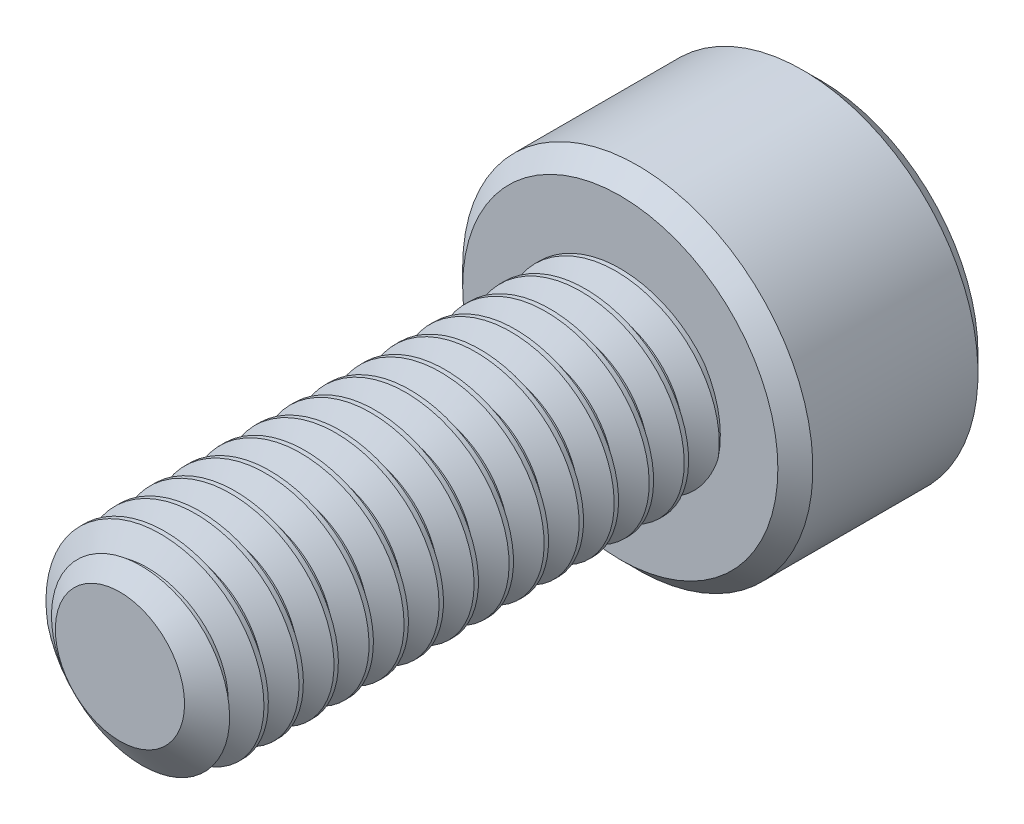
SolidWorks part; units mm, degrees
ref_plane "Front Plane" through (0, 0, 0) normal (0, 0, 1) x (1, 0, 0)
ref_plane "Top Plane" through (0, 0, 0) normal (0, 1, 0) x (1, 0, 0)
ref_plane "Right Plane" through (0, 0, 0) normal (1, 0, 0) x (0, 0, -1)
sketch "Sketch1" plane through (0, 0, 0) normal (0, 0, 1) x (1, 0, 0)
  circle A0 centre (0, 0) radius 2
  dimension "OD" = 4
extrude "Extrude1" add sketch "Sketch1" against normal blind 10
sketch "Sketch2" plane through (0, 0, 0) normal (0, 0, 1) x (1, 0, 0)
  circle A0 centre (0, 0) radius 2 construction
  circle A1 centre (0, 0) radius 2
curve "Helix/Spiral1" pitch 0.7 height 10.7 radius 2 centre (0, 0, 0) axis (0, 0, -1) start towards (0, 1, 0) parameters "pitch"=0.7
sketch "Sketch3" plane through (0, 0, 0) normal (1, 0, 0) x (0, 0, -1)
  line L0 (-0.6125, 2) -> (-0.35, 1.5453)
  line L1 (-0.35, 1.5453) -> (-0.2625, 1.5453)
  line L2 (-0.2625, 1.5453) -> (0, 2)
  line L3 (-0.6125, 2) -> (0, 2)
  line L4 (-0.3062, 2) -> (-0.3062, 1.5453) construction
  line L5 (-0.4812, 1.7727) -> (-0.1312, 1.7727) construction
  line L6 (0, 2) -> (0, -2) construction
  dimension "D1" = 0.0875
  dimension "D2" = 0.35
  dimension "D3" = 60
sweep "Cut-Sweep1" cut profiles "Sketch3" path "Helix/Spiral1" align with end faces yes
sketch "Sketch4" plane through (0, 0, 0) normal (1, 0, 0) x (0, 0, -1)
  line L0 (0.4962, 2) -> (0, 1.2913)
  line L1 (0, 1.2913) -> (0, 2)
  line L2 (0.4962, 2) -> (0, 2)
  line L3 (-0.6125, 2) -> (0, 2) construction
  line L4 (0, 0) -> (7.0209, 0) construction
  dimension "D1" = 55
  dimension "D2" = 0.254
revolve "Cut-Revolve1" cut sketch "Sketch4" angle 360 about L4
sketch "Sketch6" plane through (0, 0, -10) normal (0, 0, -1) x (-1, 0, 0)
  circle A0 centre (0, 0) radius 3.5
  dimension "head dia" = 7
extrude "Extrude2" add sketch "Sketch6" along normal blind 4
sketch "Sketch7" plane through (0, 0, -14) normal (0, 0, -1) x (-1, 0, 0)
  line L1 (0, 1.7321) -> (-1.5, 0.866)
  line L2 (-1.5, 0.866) -> (-1.5, -0.866)
  line L3 (-1.5, -0.866) -> (0, -1.7321)
  line L4 (0, -1.7321) -> (1.5, -0.866)
  line L5 (1.5, -0.866) -> (1.5, 0.866)
  line L6 (1.5, 0.866) -> (0, 1.7321)
  circle A0 centre (0, 0) radius 1.5 construction
  dimension "hex dia" = 3
extrude "Cut-Extrude1" cut sketch "Sketch7" against normal blind 2.25
sketch "Sketch8" plane through (0, 0, -14) normal (0, 0, -1) x (-1, 0, 0)
  circle A0 centre (0, 0) radius 1.7321
extrude "Cut-Extrude2" cut sketch "Sketch8" against normal through all draft 45
chamfer "Chamfer1" distance 0.35 angle 45 2 edges at (-3.5, 0, -14) (-3.5, 0, -10)
sketch "Sketch10" plane through (0, 0, -10) normal (0, 0, 1) x (1, 0, 0)
  circle A1 centre (0, 0) radius 2
  circle A2 centre (0, 0) radius 2
  dimension "D1" = 0
ref_plane "Plane1" through (0, 0, 0) normal (0, 0, 1) x (1, 0, 0)
extrude "partial thread" [suppressed] add sketch "Sketch10" along normal up to surface (10 mm away) separate body up to plane "Plane1"
chamfer "Chamfer2" [suppressed] distance 0.08 angle 45
combine bodies "Combine1" [suppressed] operation type add bodies to combine 107 108
sketch "Sketch9" plane through (0, 0, 0) normal (1, 0, 0) x (0, 0, -1)
  line L0 (0, 2) -> (0, -2) construction
  line L1 (1.75, 2) -> (1.75, -2) construction
  dimension "D1" = 1.75
equation "\"D3@Helix/Spiral1\" = \"screw length@Extrude1\"+\"pitch@Helix/Spiral1\""
equation "\"D1@Sketch3\" = \"pitch@Helix/Spiral1\"*.125"
equation "\"D2@Sketch3\" = \"pitch@Helix/Spiral1\"*.5"
equation "\"D1@Cut-Extrude1\" = \"hex dia@Sketch7\"*.75"
equation "\"D1@Chamfer1\" = \"head dia@Sketch6\"*.05"
equation "\"D1@Sketch9\" = \"pitch@Helix/Spiral1\"*2.5"
equation "\"D1@Chamfer2\"=\"OD@Sketch1\"*.02"
